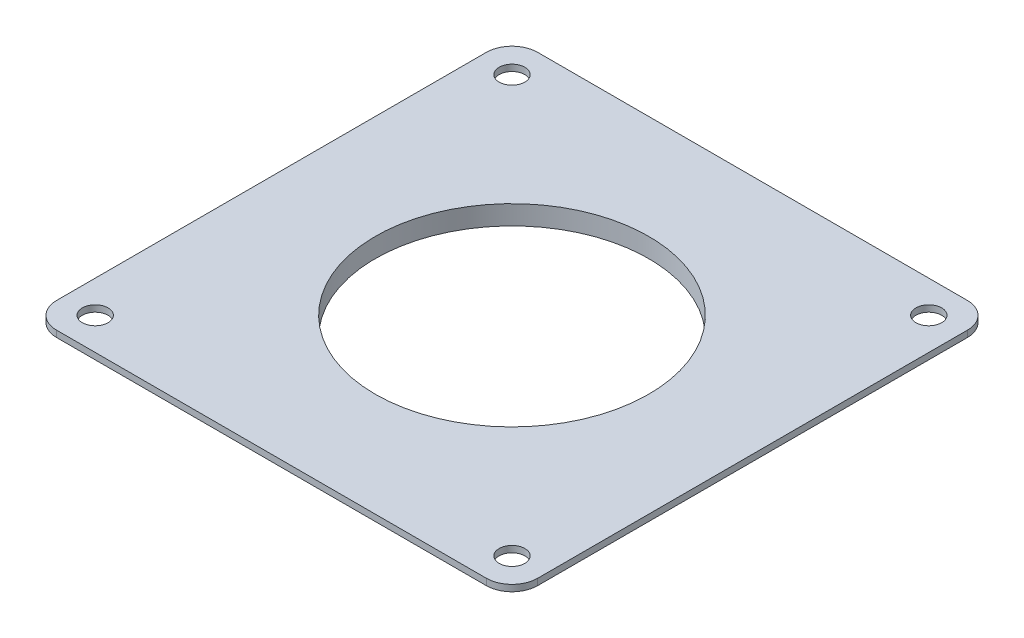
SolidWorks part; units mm, degrees
ref_plane "Front Plane" through (0, 0, 0) normal (0, 0, 1) x (1, 0, 0)
ref_plane "Top Plane" through (0, 0, 0) normal (0, 1, 0) x (1, 0, 0)
ref_plane "Right Plane" through (0, 0, 0) normal (1, 0, 0) x (0, 0, -1)
sketch "Sketch1" plane through (0, 0, 0) normal (0, 1, 0) x (1, 0, 0)
  line L1 (-42.42, -47.5) -> (42.42, -47.5)
  line L2 (-47.5, -42.42) -> (-47.5, 42.42)
  line L3 (-42.42, 47.5) -> (42.42, 47.5)
  line L4 (47.5, -42.42) -> (47.5, 42.42)
  line L5 (-47.5, -47.5) -> (47.5, 47.5) construction
  line L6 (-47.5, 47.5) -> (47.5, -47.5) construction
  arc A0 (-42.42, -47.5) -> (-47.5, -42.42) centre (-42.42, -42.42) cw
  arc A1 (42.42, -47.5) -> (47.5, -42.42) centre (42.42, -42.42) ccw
  arc A2 (42.42, 47.5) -> (47.5, 42.42) centre (42.42, 42.42) cw
  arc A3 (-47.5, 42.42) -> (-42.42, 47.5) centre (-42.42, 42.42) cw
  point P0 (0, 0)
  dimension "D3" = 5.08
  dimension "D1" = 95
  dimension "D2" = 95
extrude "Boss-Extrude1" add sketch "Sketch1" along normal blind 1.27
sketch "Sketch2" plane through (0, 0, 0) normal (0, -1, 0) x (1, 0, 0)
  circle A0 centre (0, 0) radius 38.1
  dimension "D1" = 76.2
extrude "Boss-Extrude2" add sketch "Sketch2" along normal blind 2.54
fillet "Fillet1" radius 10.16 1 edges at (0, 0, -38.1)
sketch "Sketch3" plane through (0, 1.27, 0) normal (0, 1, 0) x (1, 0, 0)
  circle A0 centre (0, 0) radius 27
  dimension "D1" = 54
extrude "Cut-Extrude1" cut sketch "Sketch3" against normal through all
sketch "Sketch4" plane through (0, 1.27, 0) normal (0, 1, 0) x (1, 0, 0)
  line L0 (-61.4593, 0) -> (61.4593, 0) construction
  line L1 (0, -51.5197) -> (0, 51.5197) construction
  line L2 (42.42, 47.5) -> (-42.42, 47.5) construction
  line L3 (-47.5, 42.42) -> (-47.5, -42.42) construction
  circle A0 centre (-41.15, 41.15) radius 2.54
  circle A2 centre (41.15, 41.15) radius 2.54
  circle A3 centre (-41.15, -41.15) radius 2.54
  circle A4 centre (41.15, -41.15) radius 2.54
  point P5 (0, 0)
  point P9 (0, 0)
  dimension "D1" = 5.08
  dimension "D2" = 6.35
  dimension "D3" = 6.35
extrude "Cut-Extrude2" cut sketch "Sketch4" against normal through all
